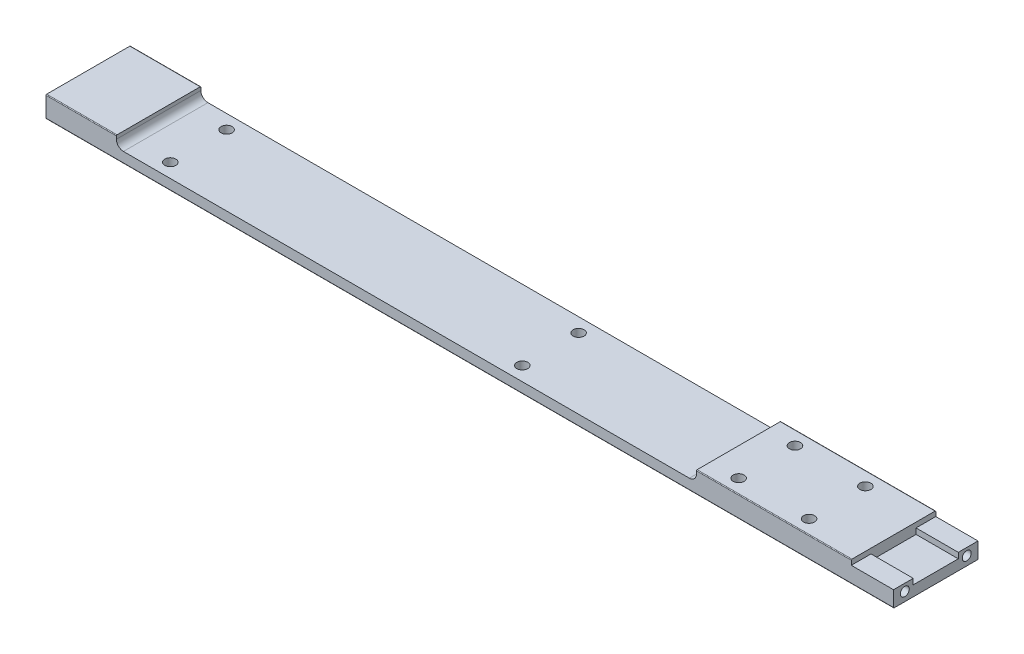
SolidWorks part; units mm, degrees
material "6061 Alloy"
ref_plane "Front Plane" through (0, 0, 0) normal (0, 0, 1) x (1, 0, 0)
ref_plane "Top Plane" through (0, 0, 0) normal (0, 1, 0) x (1, 0, 0)
ref_plane "Right Plane" through (0, 0, 0) normal (1, 0, 0) x (0, 0, -1)
sketch "Sketch1" plane through (0, 0, 0) normal (0, 1, 0) x (1, 0, 0)
  line L1 (191.135, -19.05) -> (-191.135, -19.05)
  line L2 (191.135, -19.05) -> (191.135, 19.05)
  line L3 (191.135, 19.05) -> (-191.135, 19.05)
  line L4 (-191.135, -19.05) -> (-191.135, 19.05)
  line L5 (191.135, -19.05) -> (-191.135, 19.05) construction
  line L6 (191.135, 19.05) -> (-191.135, -19.05) construction
  point P0 (0, 0)
  dimension "Length" = 382.27
  dimension "Width" = 38.1
sketch "Sketch2" plane through (0, 0, 0) normal (1, 0, 0) x (0, 0, -1)
  line L0 (19.05, 4.7625) -> (19.05, -4.7625) construction
  point P2 (19.05, 0)
  dimension "Thickness" = 9.525
sketch "Sketch3" plane through (0, 0, 0) normal (0, 1, 0) x (1, 0, 0)
  line L1 (-191.135, 19.05) -> (191.135, 19.05)
  line L2 (-191.135, 19.05) -> (-191.135, -19.05)
  line L3 (-191.135, -19.05) -> (191.135, -19.05)
  line L4 (191.135, 19.05) -> (191.135, -19.05)
extrude "Boss-Extrude1" add sketch "Sketch3" against normal up to vertex (4.7625 mm away) and the other way up to vertex (4.7625 mm away) up to point (0, -4.7625, -19.05) other way up to point (0, 4.7625, -19.05)
fillet "Fillet1" radius 0.3143 4 edges at (0, -4.7625, 19.05) (0, -4.7625, -19.05) (0, 4.7625, -19.05) (0, 4.7625, 19.05)
sketch "Sketch4" plane through (-191.135, 0, 0) normal (-1, 0, 0) x (0, 0, 1)
  line L0 (0, -0.762) -> (13.97, -0.762) construction
  line L1 (0, -0.762) -> (-13.97, -0.762) construction
  line L2 (0, -0.762) -> (0, 0) construction
  dimension "D1" = 13.97
  dimension "D2" = 13.97
  dimension "D3" = 0.762
hole_wizard "Tap Drill for #10-32 Tap1" positions "Sketch5" profile "Sketch6" hole size "#10-32" standard "ANSI Inch"
sketch "Sketch5" plane through (-191.135, 0, 0) normal (-1, 0, 0) x (0, 0, 1)
  point P0 (-13.97, -0.762)
  point P3 (13.97, -0.762)
sketch "Sketch6" plane through (-191.135, -0.762, -13.97) normal (0, 1, 0) x (0, 0, 1)
  line L0 (0, 0) -> (0, 26.6133)
  line L1 (0, 26.6133) -> (2.0193, 25.4)
  line L2 (2.0193, 25.4) -> (2.0193, 0)
  line L5 (2.0193, 0) -> (0, 0)
  line L10 (0, 26.6133) -> (-2.0193, 25.4) construction
  line L11 (0, -6.35) -> (0, 107.95) construction
  dimension "Hole Dia." = 4.0386
  dimension "Hole Depth" = 25.4
  dimension "Drill Angle" = 118
hole_wizard "Tap Drill for #10-32 Tap2" positions "Sketch7" profile "Sketch8" hole size "#10-32" standard "ANSI Inch"
sketch "Sketch7" plane through (191.135, 0, 0) normal (1, 0, 0) x (0, 0, -1)
  point P0 (-13.97, -0.762)
  point P3 (13.97, -0.762)
sketch "Sketch8" plane through (191.135, -0.762, 13.97) normal (0, 1, 0) x (0, 0, -1)
  line L0 (0, 0) -> (0, 26.6133)
  line L1 (0, 26.6133) -> (2.0193, 25.4)
  line L2 (2.0193, 25.4) -> (2.0193, 0)
  line L5 (2.0193, 0) -> (0, 0)
  line L10 (0, 26.6133) -> (-2.0193, 25.4) construction
  line L11 (0, -6.35) -> (0, 107.95) construction
  dimension "Hole Dia." = 4.0386
  dimension "Hole Depth" = 25.4
  dimension "Drill Angle" = 118
sketch "Sketch10" plane through (0, 0, -19.05) normal (0, 0, -1) x (-1, 0, 0)
  line L0 (159.385, 4.7625) -> (159.385, 3.175)
  line L1 (-191.135, 4.7625) -> (191.135, 4.7625) construction
  line L2 (156.21, 0) -> (-99.06, 0)
  line L3 (-102.235, 3.175) -> (-102.235, 4.7625)
  line L4 (-102.235, 4.7625) -> (159.385, 4.7625)
  line L5 (-191.135, -4.7625) -> (-191.135, 33.0219) construction
  line L6 (191.135, -4.7625) -> (191.135, 33.0219) construction
  line L7 (-191.135, 4.7625) -> (-172.085, 4.7625)
  line L8 (-172.085, 4.7625) -> (-172.085, 2.4765)
  line L9 (-172.085, 2.4765) -> (-191.135, 2.4765)
  line L10 (-191.135, -4.4482) -> (-191.135, 4.4482) construction
  line L11 (-191.135, 2.4765) -> (-191.135, 4.7625)
  arc A0 (159.385, 3.175) -> (156.21, 0) centre (156.21, 3.175) cw
  arc A1 (-99.06, 0) -> (-102.235, 3.175) centre (-99.06, 3.175) cw
  point P12 (159.385, 0)
  dimension "D4" = 3.175
  dimension "D1" = 88.9
  dimension "D2" = 31.75
  dimension "D3" = 4.7625
  dimension "D5" = 19.05
  dimension "D6" = 2.286
extrude "Cut-Extrude1" cut sketch "Sketch10" against normal through all
sketch "Sketch13" plane through (0, -4.7625, 0) normal (0, -1, 0) x (1, 0, 0)
  line L0 (191.135, 0) -> (146.685, 0) construction
  line L1 (191.135, 18.7357) -> (191.135, -18.7357) construction
  line L2 (146.685, 0) -> (146.685, 12.7) construction
  line L3 (146.685, 12.7) -> (114.935, 12.7) construction
  line L4 (114.935, 12.7) -> (114.935, -12.7) construction
  line L5 (114.935, -12.7) -> (146.685, -12.7) construction
  line L6 (146.685, -12.7) -> (146.685, 0) construction
  dimension "D1" = 44.45
  dimension "D2" = 31.75
  dimension "D3" = 31.75
hole_wizard "#10 Clearance Hole1" positions "Sketch14" profile "Sketch15" hole size "#10" standard "ANSI Inch" end condition through all
sketch "Sketch14" plane through (0, -4.7625, 0) normal (0, -1, 0) x (-1, 0, 0)
  point P0 (-114.935, 12.7)
  point P3 (-146.685, 12.7)
  point P6 (-146.685, -12.7)
  point P9 (-114.935, -12.7)
sketch "Sketch15" plane through (114.935, -4.7625, -12.7) normal (1, 0, 0) x (0, 0, -1)
  line L0 (0, 0) -> (0, 9.525)
  line L1 (0, 9.525) -> (2.4892, 9.525)
  line L2 (2.4892, 9.525) -> (2.4892, 3.1411)
  line L3 (2.4892, 3.1411) -> (5.2197, 0)
  line L5 (5.2197, 0) -> (0, 0)
  line L6 (-2.4892, 3.1411) -> (-5.2197, 0) construction
  line L11 (0, -6.35) -> (0, 107.95) construction
  dimension "Thru Hole Dia." = 4.9784
  dimension "Thru Hole Depth" = 9.525
  dimension "Near C'Sink Dia." = 10.4394
  dimension "Near C'Sink Angle" = 82
sketch "Sketch17" plane through (0, 2.4765, 0) normal (0, 1, 0) x (1, 0, 0)
  line L23 (191.135, 0) -> (191.135, 10.16)
  line L24 (191.135, -19.05) -> (191.135, 19.05) construction
  line L25 (191.135, 10.16) -> (172.085, 10.16)
  line L26 (172.085, -19.05) -> (172.085, 19.05) construction
  line L27 (172.085, 10.16) -> (172.085, -10.16)
  line L28 (172.085, -10.16) -> (191.135, -10.16)
  line L29 (191.135, -10.16) -> (191.135, 0)
extrude "Cut-Extrude2" cut sketch "Sketch17" against normal blind 2.54
sketch "Sketch18" plane through (0, 0, 0) normal (0, 1, 0) x (1, 0, 0)
  line L0 (30.0312, 19.05) -> (17.3312, 19.05) construction
  line L1 (99.06, 19.05) -> (-156.21, 19.05) construction
  line L2 (30.0312, 19.584) -> (30.0312, 16.7333) construction
  line L3 (17.3312, 19.05) -> (17.3312, 12.7) construction
  line L4 (17.3312, 12.7) -> (17.3312, -12.7) construction
  line L5 (17.3312, -12.7) -> (17.3312, -19.05) construction
  line L6 (99.06, -19.05) -> (-156.21, -19.05) construction
  line L7 (17.3312, -19.05) -> (-141.4188, -19.05) construction
  line L8 (-141.4188, -19.05) -> (-141.4188, -12.7) construction
  line L9 (-141.4188, -12.7) -> (-141.4188, 12.7) construction
  line L10 (-141.4188, 12.7) -> (-141.4188, 19.05) construction
  dimension "D1" = 6.35
  dimension "D2" = 25.4
  dimension "D3" = 6.35
  dimension "D4" = 25.4
hole_wizard "#10 Clearance Hole2" positions "Sketch19" profile "Sketch20" hole size "#10" standard "ANSI Inch" end condition through all
sketch "Sketch19" plane through (0, 0, 0) normal (0, 1, 0) x (1, 0, 0)
  point P0 (-141.4188, 12.7)
  point P3 (-141.4188, -12.7)
  point P6 (17.3312, 12.7)
  point P9 (17.3312, -12.7)
sketch "Sketch20" plane through (-141.4188, 0, -12.7) normal (1, 0, 0) x (0, 0, 1)
  line L0 (0, 0) -> (0, 4.7625)
  line L1 (0, 4.7625) -> (2.4892, 4.7625)
  line L2 (2.4892, 4.7625) -> (2.4892, 0)
  line L5 (2.4892, 0) -> (0, 0)
  line L11 (0, -6.35) -> (0, 107.95) construction
  dimension "Thru Hole Dia." = 4.9784
  dimension "Thru Hole Depth" = 4.7625
equation "\"D1@Fillet1\" = \"Thickness@Sketch2\" * .033"
